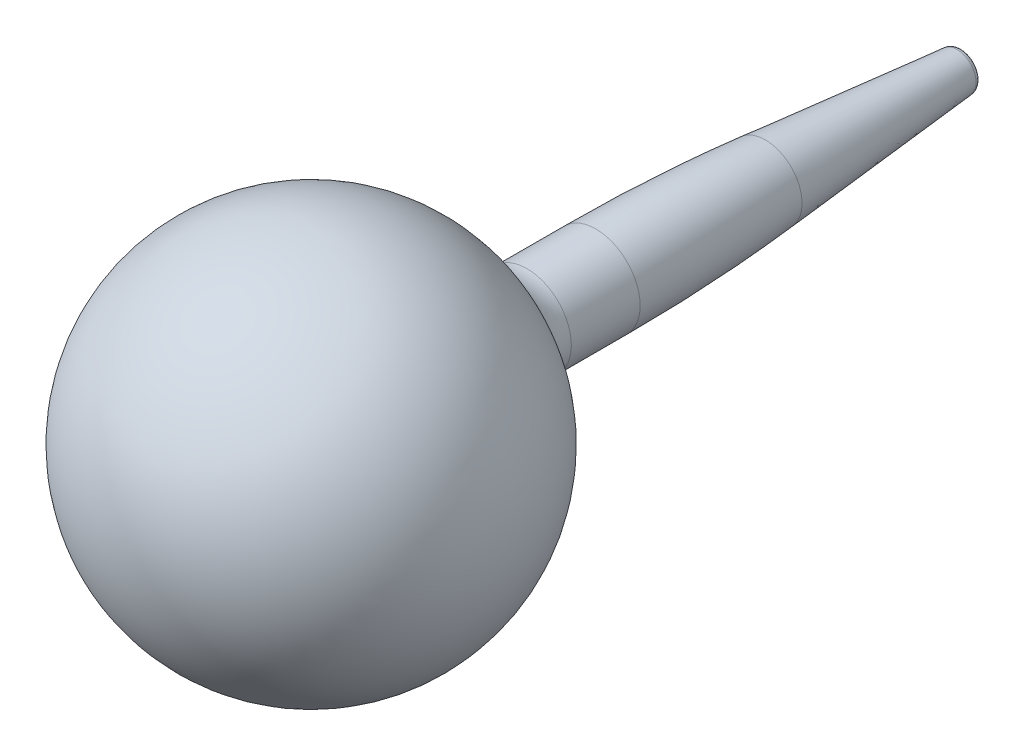
SolidWorks part; units mm, degrees
ref_plane "Front Plane" through (0, 0, 0) normal (0, 0, 1) x (1, 0, 0)
ref_plane "Top Plane" through (0, 0, 0) normal (0, 1, 0) x (1, 0, 0)
ref_plane "Right Plane" through (0, 0, 0) normal (1, 0, 0) x (0, 0, -1)
sketch "Sketch1" plane through (0, 0, 0) normal (0, 0, 1) x (1, 0, 0)
  circle A0 centre (0, 0) radius 6
  dimension "D1" = 12
extrude "Boss-Extrude1" add sketch "Sketch1" along normal blind 63.5
sketch "Sketch2" plane through (0, 0, 0) normal (1, 0, 0) x (0, 0, -1)
  line L0 (-63.5, 0) -> (-113.5812, 0)
  line L1 (-63.5, 6) -> (-63.5, -6) construction
  line L2 (-63.5, 6) -> (-63.5, 0)
  arc A1 (-113.5812, 0) -> (-63.5, 6) centre (-88.1812, 0) cw
  dimension "D1" = 25.4
revolve "Revolve1" add sketch "Sketch2" angle 360 about L0
sketch "Sketch3" plane through (0, 0, 0) normal (0, 0, -1) x (-1, 0, 0)
  line L1 (-0.7, 1.1) -> (0.7, 1.1)
  line L2 (-0.7, 1.1) -> (-0.7, -1.1)
  line L3 (-0.7, -1.1) -> (0.7, -1.1)
  line L4 (0.7, 1.1) -> (0.7, -1.1)
  point P2 (0.7, 0)
  point P5 (0, 1.1)
  dimension "D1" = 1.4
  dimension "D2" = 2.2
extrude "Cut-Extrude1" cut sketch "Sketch3" against normal blind 50.8
fillet "Fillet1" radius 6.35 1 edges at (6, 0, 63.5)
sketch "Sketch5" plane through (0, 0, 0) normal (0, 1, 0) x (1, 0, 0)
  line L0 (0, 0) -> (0, -38.1) construction
  line L1 (6, 0) -> (-6, 0) construction
  line L2 (0, -38.1) -> (-6, -38.1) construction
  line L3 (-6, 0) -> (-6, -58.9316) construction
  line L4 (-6, -38.1) -> (-2.54, 0)
  line L5 (-2.54, 0) -> (0, 0) construction
  line L6 (-6, -38.1) -> (-6, 0)
  line L7 (-6, 0) -> (-2.54, 0)
  point P4 (-2.54, 0)
  dimension "D1" = 2.54
  dimension "D2" = 38.1
revolve "Cut-Revolve1" cut sketch "Sketch5" angle 360 about L0
fillet "Fillet2" radius 254 1 edges at (-6, 0, 38.1)
fillet "Fillet3" radius 0.762 1 edges at (-2.54, 0, 0)
